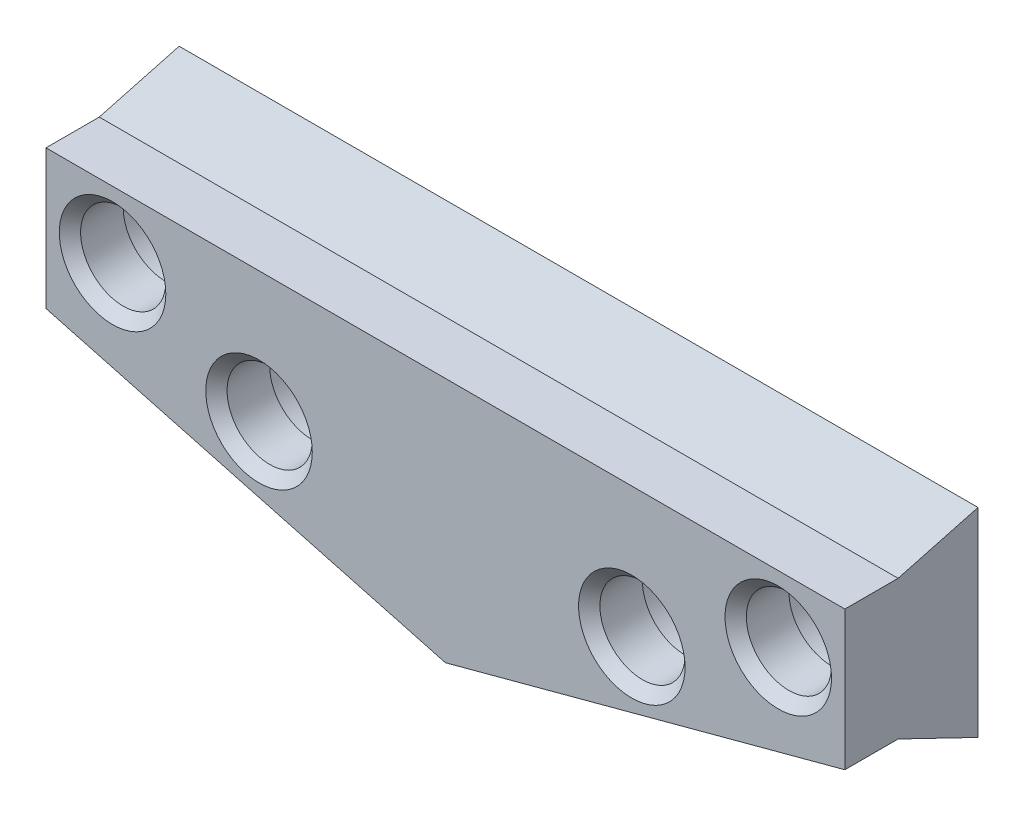
SolidWorks part; units mm, degrees
ref_plane "Plano frontal" through (0, 0, 0) normal (0, 0, 1) x (1, 0, 0)
ref_plane "Plano superior" through (0, 0, 0) normal (0, 1, 0) x (1, 0, 0)
ref_plane "Plano direito" through (0, 0, 0) normal (1, 0, 0) x (0, 0, -1)
sketch "Esboço1" plane through (0, 0, 0) normal (0, 0, 1) x (1, 0, 0)
  line L0 (-15, 13) -> (-15, 4.0192)
  line L1 (-15, 4.0192) -> (0, 0)
  line L2 (0, 0) -> (0, 13) construction
  line L3 (15, 13) -> (-15, 13)
  line L4 (15, 4.0192) -> (0, 0)
  line L5 (15, 13) -> (15, 4.0192)
  dimension "D1" = 150
  dimension "D2" = 30
  dimension "D3" = 13
extrude "Ressalto-extrusão1" add sketch "Esboço1" along normal blind 3
chamfer "Chanfro1" distance 5 angle 25 2 edges at (-7.5, 2.0096, 3) (7.5, 2.0096, 3) first distance on face at (-7.5, 2.0096, 1.5) first distance on face at (7.5, 2.0096, 1.5)
chamfer "Chanfro2" distance 5 angle 15 1 edges at (0, 13, 3) first distance on face at (0, 13, 1.5)
sketch "Esboço2" plane through (0, 0, 3) normal (0, 0, 1) x (1, 0, 0)
  line L0 (15, 11.6603) -> (-15, 11.6603) construction
  line L1 (-15, 6.433) -> (15, 6.433) construction
  line L2 (-15, 6.433) -> (-15, 11.6603)
  line L3 (-15, 11.6603) -> (15, 11.6603)
  line L4 (15, 6.433) -> (15, 11.6603)
  line L5 (-15, 6.433) -> (15, 11.6603) construction
  line L6 (-15, 11.6603) -> (15, 6.433) construction
  line L7 (0, 2.4138) -> (15, 6.433) construction
  line L8 (-15, 6.433) -> (0, 2.4138) construction
  line L9 (0, 2.4138) -> (15, 6.433)
  line L10 (-15, 6.433) -> (0, 2.4138)
  point P0 (0, 9.0466)
  line M5 (15, 6.433) -> (15, 11.6603)
  line M6 (15, 11.6603) -> (-15, 11.6603)
  line M7 (-15, 11.6603) -> (-15, 6.433)
  line M8 (-15, 6.433) -> (0, 2.4138)
  line M9 (0, 2.4138) -> (15, 6.433)
  dimension "D1" = 30
extrude "Ressalto-extrusão2" add sketch "Esboço2" along normal blind 2 contours M9 M5 M6 M7 M8 region at (0, 7.9488, 3)
sketch "Esboço3" plane through (0, 0, 0) normal (0, 0, 1) x (1, 0, 0)
  line L0 (0, 0) -> (0, 25.7319) construction
  line L2 (15, 11.6603) -> (-15, 11.6603) construction
  line L3 (-9.3246, 9.1603) -> (-10.9123, 11.9103) construction
  line L4 (-10.9123, 11.9103) -> (-14.0877, 11.9103) construction
  line L5 (-14.0877, 11.9103) -> (-15.6754, 9.1603) construction
  line L6 (-15.6754, 9.1603) -> (-14.0877, 6.4103) construction
  line L7 (-14.0877, 6.4103) -> (-10.9123, 6.4103) construction
  line L8 (-10.9123, 6.4103) -> (-9.3246, 9.1603) construction
  circle A0 centre (-7, 6.7623) radius 1.6
  circle A1 centre (7, 6.7623) radius 1.6
  circle A2 centre (-12.5, 9.1603) radius 1.6
  circle A3 centre (12.5, 9.1603) radius 1.6
  circle A4 centre (-7, 6.7623) radius 2.75 construction
  circle A5 centre (-12.5, 9.1603) radius 2.75 construction
  dimension "D2" = 3.2
  dimension "D5" = 5.5
  dimension "D6" = 5.5
  dimension "D7" = 0.5
  dimension "D1" = 14
  dimension "D3" = 2.5
  dimension "D4" = 25
extrude "Corte-extrusão1" cut sketch "Esboço3" along normal through all both and the other way through all
sketch "Esboço4" plane through (0, 0, 0) normal (0, 0, -1) x (-1, 0, 0)
  line L0 (0, 0) -> (0, 23.2948) construction
  circle A2 centre (-7, 6.7623) radius 2
  circle A4 centre (12.5, 9.1603) radius 2
  circle A5 centre (-12.5, 9.1603) radius 2
  circle A6 centre (7, 6.7623) radius 2
  dimension "D2" = 4
extrude "Corte-extrusão2" cut sketch "Esboço4" against normal blind 3 from surface starting at face at (14.1, 9.1603, 0)
sketch "Esboço6" plane through (0, 0, 0) normal (0, 0, -1) x (-1, 0, 0)
  line L1 (-2.8, 10) -> (2.8, 10)
  line L2 (-2.8, 10) -> (-2.8, 4)
  line L3 (-2.8, 4) -> (2.8, 4)
  line L4 (2.8, 10) -> (2.8, 4)
  line L5 (-2.8, 10) -> (2.8, 4) construction
  line L6 (-2.8, 4) -> (2.8, 10) construction
  point P0 (0, 7)
  dimension "D1" = 5.6
  dimension "D2" = 6
  dimension "D3" = 4
extrude "Corte-extrusão3" cut sketch "Esboço6" against normal blind 2
chamfer "Chanfro3" distance 0.4 angle 45 4 edges at (10.9, 9.1603, 5) (5.4, 6.7623, 5) (-5.4, 6.7623, 5) (-10.9, 9.1603, 5)
